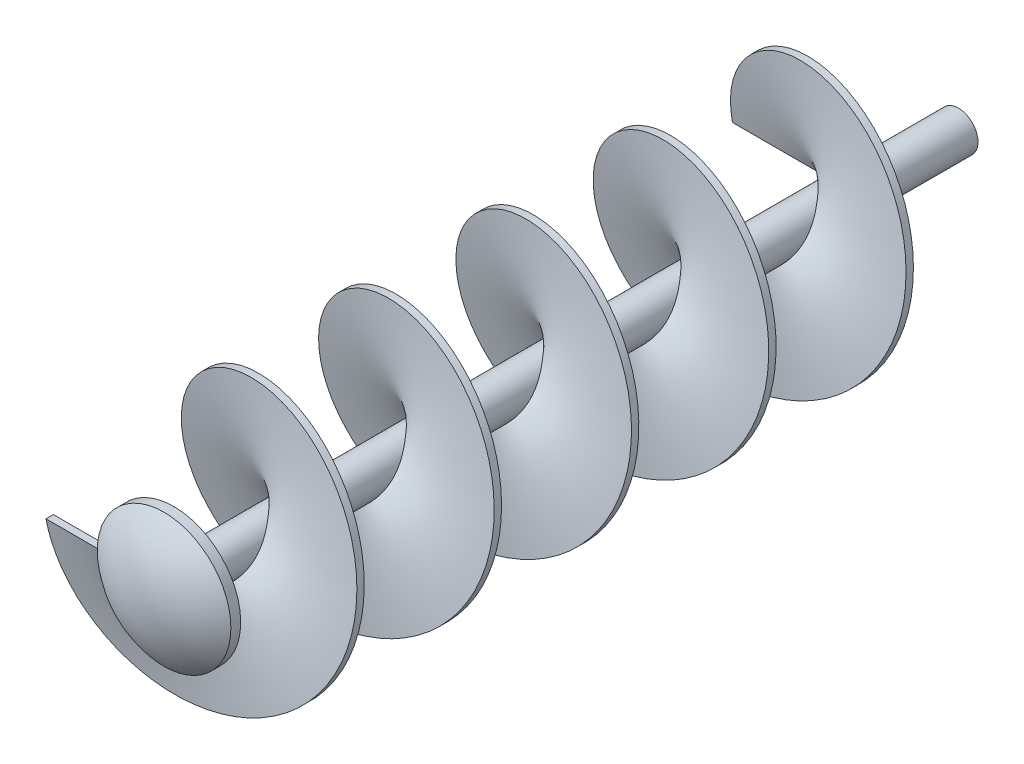
SolidWorks part; units mm, degrees
ref_plane "Front Plane" through (0, 0, 0) normal (0, 0, 1) x (1, 0, 0)
ref_plane "Top Plane" through (0, 0, 0) normal (0, 1, 0) x (1, 0, 0)
ref_plane "Right Plane" through (0, 0, 0) normal (1, 0, 0) x (0, 0, -1)
sketch "Sketch1" plane through (0, 0, 0) normal (0, 0, 1) x (1, 0, 0)
  circle A0 centre (0, 0) radius 4
  dimension "D1" = 8
extrude "Boss-Extrude1" add sketch "Sketch1" along normal blind 140
sketch "Sketch8" plane through (0, 0, 140) normal (0, 0, 1) x (1, 0, 0)
  circle A0 centre (0, 0) radius 4
extrude "Boss-Extrude2" add sketch "Sketch8" along normal blind 10
ref_plane "Plane3" through (0, 0, 10) normal (0, 0, 1) x (1, 0, 0)
sketch "Sketch16" plane through (0, 0, 10) normal (0, 0, 1) x (1, 0, 0)
  circle A0 centre (0, 0) radius 4
curve "Helix/Spiral3" pitch 28 height 140 radius 4 left hand yes centre (0, 0, 10) axis (0, 0, 1) start towards (-1, 0, 0)
ref_plane "Plane4" through (0, 0, 130) normal (0, 0, 1) x (1, 0, 0)
sketch "Sketch57" plane through (0, 0, 0) normal (0, 1, 0) x (1, 0, 0)
  line L0 (-3.9994, -11.5864) -> (-24.4994, -11.5864)
  line L1 (-3.9994, -11.5864) -> (-3.9994, -10.0864)
  line L2 (-24.4994, -11.5864) -> (-24.4994, -10.0864)
  line L3 (-3.9994, -10.0864) -> (-24.4994, -10.0864)
  dimension "D1" = 1.5
  dimension "D2" = 20.5
sweep "Sweep8" add profiles "Sketch57" path "Helix/Spiral3"
sketch "Sketch63" plane through (0, 0, 150) normal (0, 0, 1) x (1, 0, 0)
  circle A0 centre (0, 0) radius 13.6206
extrude "Boss-Extrude5" add sketch "Sketch63" along normal blind 2
sketch "Sketch64" plane through (0, 0, 0) normal (0, 0, -1) x (-1, 0, 0)
  circle A0 centre (0, 0) radius 4
extrude "Boss-Extrude6" add sketch "Sketch64" along normal blind 10
sketch "Sketch65" plane through (0, 0, -10) normal (0, 0, -1) x (-1, 0, 0)
  circle A0 centre (0, 0) radius 1
  dimension "D1" = 2
extrude "Cut-Extrude1" cut sketch "Sketch65" against normal blind 10
dome "Dome1" faces to dome 1 distance 5 reverse direction no elliptical dome no face at (13.6206, 0, 152) parameters "D1"=5
